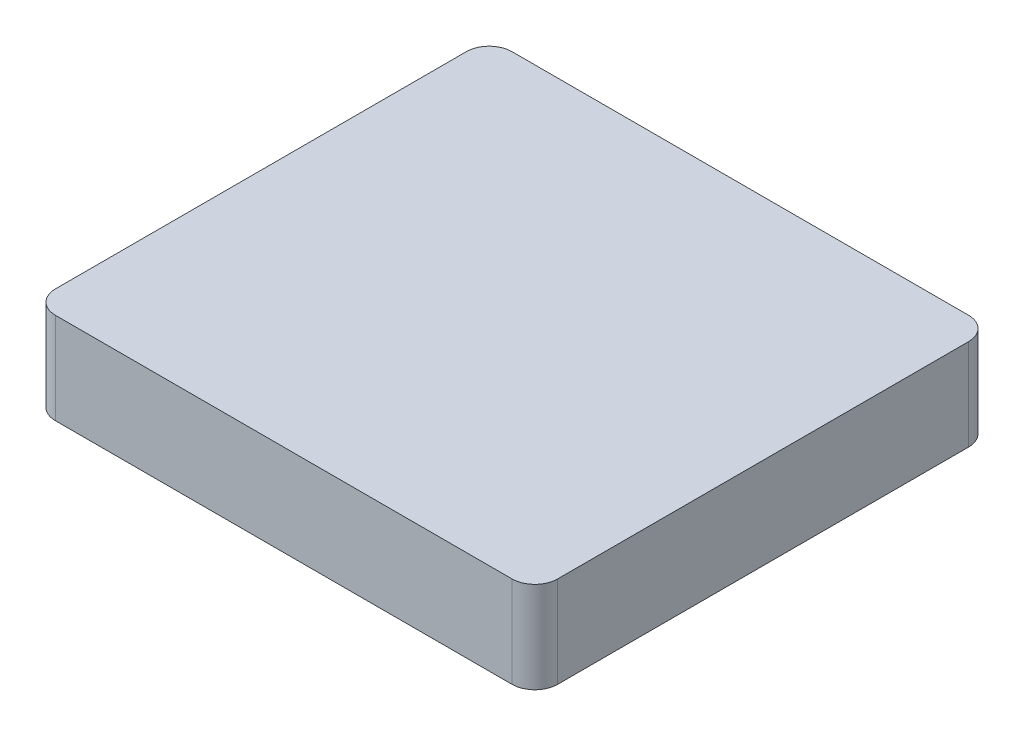
SolidWorks part; units mm, degrees
ref_plane "Front Plane" through (0, 0, 0) normal (0, 0, 1) x (1, 0, 0)
ref_plane "Top Plane" through (0, 0, 0) normal (0, 1, 0) x (1, 0, 0)
ref_plane "Right Plane" through (0, 0, 0) normal (1, 0, 0) x (0, 0, -1)
sketch "Sketch1" plane through (0, 0, 0) normal (0, 1, 0) x (1, 0, 0)
  line L0 (0, 0) -> (13.97, 0)
  line L1 (13.97, 0) -> (13.97, 12.7)
  line L2 (13.97, 12.7) -> (0, 12.7)
  line L3 (0, 12.7) -> (0, 0)
  dimension "D1" = 13.97
  dimension "D2" = 12.7
extrude "Boss-Extrude1" add sketch "Sketch1" along normal blind 2.54
fillet "Fillet1" radius 0.635 4 edges at (0, 1.27, -12.7) (13.97, 1.27, -12.7) (13.97, 1.27, 0) (0, 1.27, 0)
shell "Shell1" thickness 0.635 removed face at (6.985, 0, -6.35)
sketch "Sketch2" plane through (0, 1.905, 0) normal (0, -1, 0) x (-1, 0, 0)
  line L0 (-0.635, 6.35) -> (-13.335, 6.35) construction
  line L1 (-0.635, 12.065) -> (-0.635, 0.635) construction
  line L2 (-13.335, 0.635) -> (-13.335, 12.065) construction
  line L3 (-6.985, 0.635) -> (-6.985, 12.065) construction
  line L4 (-0.635, 0.635) -> (-13.335, 0.635) construction
  line L5 (-13.335, 12.065) -> (-0.635, 12.065) construction
  circle A0 centre (-6.985, 6.35) radius 2.54
  dimension "D1" = 5.08
extrude "Boss-Extrude2" add sketch "Sketch2" along normal up to surface (1.905 mm away) up to face at (6.985, 0, -6.35)
